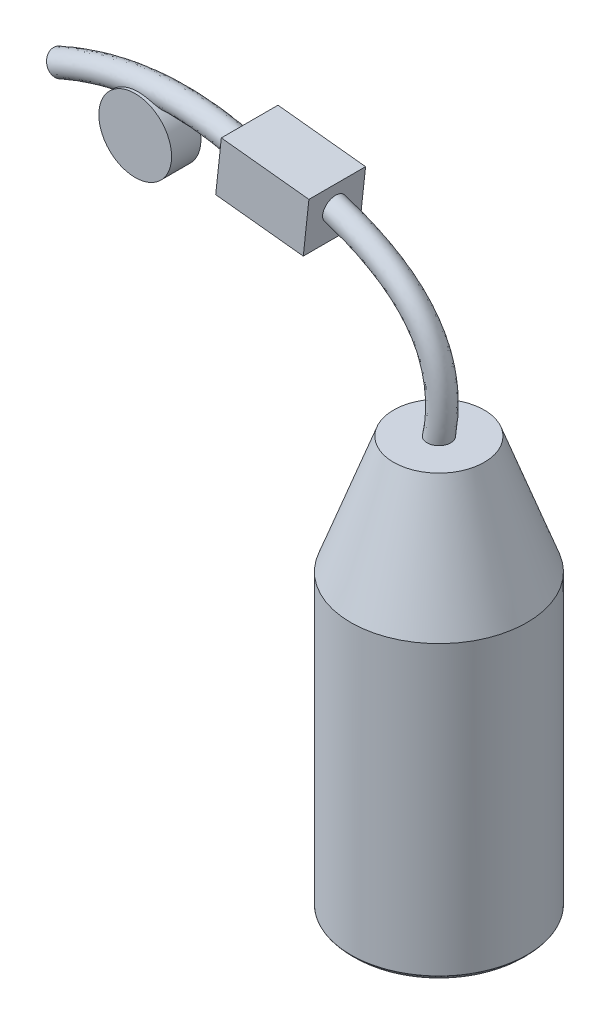
SolidWorks part; units mm, degrees
ref_plane "Front Plane" through (0, 0, 0) normal (0, 0, 1) x (1, 0, 0)
ref_plane "Top Plane" through (0, 0, 0) normal (0, 1, 0) x (1, 0, 0)
ref_plane "Right Plane" through (0, 0, 0) normal (1, 0, 0) x (0, 0, -1)
sketch "Sketch1" plane through (0, 0, 0) normal (0, 1, 0) x (1, 0, 0)
  circle A0 centre (0, 0) radius 30
  dimension "D1" = 60
extrude "Boss-Extrude1" add sketch "Sketch1" along normal blind 100
extrude "Boss-Extrude2" add sketch "Sketch1<2>" along normal blind 40 draft 20 from surface starting at face at (0, 100, 30)
sketch "Sketch1<2>" plane through (0, 0, 0) normal (0, 1, 0) x (1, 0, 0) same geometry as "Sketch1"
fillet "Fillet1" radius 2 1 edges at (0, 0, 30) second distance 2 conic rho 0.1 first distance on face at (0, 0, 30)
sketch "Sketch3" plane through (0, 140, 0) normal (0, 1, 0) x (1, 0, 0)
  circle A0 centre (0, 0) radius 4
  dimension "D1" = 8
sketch "Sketch4" plane through (0, 0, 0) normal (0, 0, 1) x (1, 0, 0)
  line L0 (4, 140) -> (-4, 140) construction
  spline S0 degree 2 poles (0, 140) (7.1291, 176.1708) (-35.5971, 189.4874) knots 0 0 0 1 1 1
  point P2 (0, 0)
  point P4 (0, 158.8198)
  point P5 (0, 0)
  point P8 (-35.5971, 189.4874)
sweep "Sweep1" add profiles "Sketch3" path "Sketch4"
sketch "Sketch5" plane through (-55.4062, 5.981, 0) normal (-0.9942, 0.1073, 0) x (0, 0, 1)
  line L1 (-9.7773, 192.3551) -> (9.5261, 192.3551)
  line L2 (-9.7773, 192.3551) -> (-9.7773, 174.5441)
  line L3 (-9.7773, 174.5441) -> (9.5261, 174.5441)
  line L4 (9.5261, 192.3551) -> (9.5261, 174.5441)
  line L5 (-9.7773, 192.3551) -> (9.5261, 174.5441) construction
  line L6 (-9.7773, 174.5441) -> (9.5261, 192.3551) construction
  point P4 (-0.1256, 183.4496)
extrude "Boss-Extrude3" add sketch "Sketch5" along normal blind 30
sketch "Sketch6" plane through (0, 0, 0) normal (0, 0, 1) x (1, 0, 0)
  line L0 (-66.5001, 182.7367) -> (-64.5885, 200.4449) construction
  spline S0 degree 2 poles (-65.5443, 191.5908) (-96.8016, 199.9906) (-129.1032, 185.6556) knots 0 0 0 1 1 1
  point P2 (-129.1032, 185.6556)
sketch "Sketch7" plane through (-85.233, 9.2007, 0) normal (-0.9942, 0.1073, 0) x (0, 0, 1)
  circle A0 centre (0, 183.4496) radius 4
  dimension "D1" = 8
sweep "Sweep3" add profiles "Sketch7" path "Sketch6"
sketch "Sketch10" plane through (0, 0, 0) normal (0, 0, 1) x (1, 0, 0)
  circle A0 centre (-98.4474, 181.9375) radius 12.3936
extrude "Boss-Extrude4" add sketch "Sketch10" along normal blind 10 from offset 5 offset against normal yes
